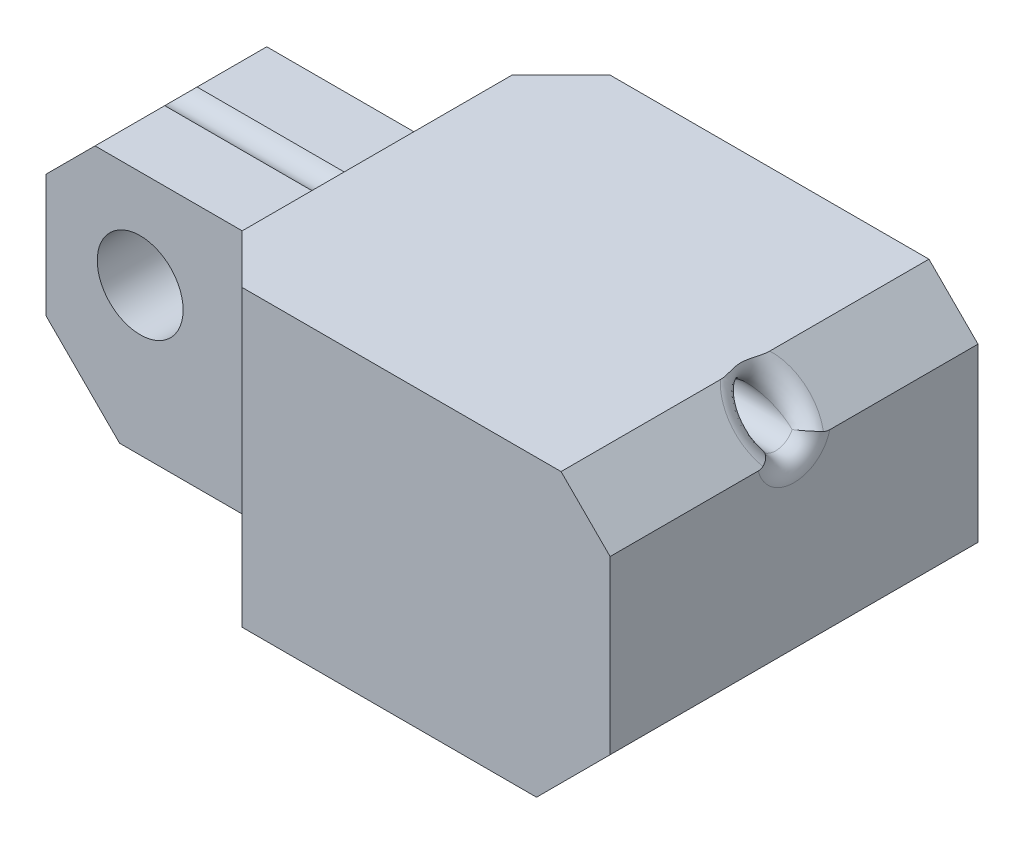
SolidWorks part; units mm, degrees
ref_plane "Спереди" through (0, 0, 0) normal (0, 0, 1) x (1, 0, 0)
ref_plane "Сверху" through (0, 0, 0) normal (0, 1, 0) x (1, 0, 0)
ref_plane "Справа" through (0, 0, 0) normal (1, 0, 0) x (0, 0, -1)
sketch "Эскиз2" plane through (0, 0, 0) normal (1, 0, 0) x (0, 0, -1)
  line L1 (-7.5, 6) -> (7.5, 6)
  line L2 (-7.5, 6) -> (-7.5, -6)
  line L3 (-7.5, -6) -> (7.5, -6)
  line L4 (7.5, 6) -> (7.5, -6)
  line L5 (-7.5, 6) -> (7.5, -6) construction
  line L6 (-7.5, -6) -> (7.5, 6) construction
  point P0 (0, 0)
extrude "Вытянуть1" add sketch "Эскиз2" along normal blind 27
sketch "Эскиз3" plane through (0, 6, 0) normal (0, 1, 0) x (1, 0, 0)
  line L0 (0, 0) -> (-9.2006, 0) construction
  line L1 (10, -9.9613) -> (10, -3.5)
  line L2 (-3.345, 9.9613) -> (10, 9.9613)
  line L3 (-3.345, 9.9613) -> (-3.345, 3.5)
  line L4 (-3.345, 3.5) -> (10, 3.5)
  line L5 (10, 9.9613) -> (10, 3.5)
  line L6 (-3.345, -9.9613) -> (10, -9.9613)
  line L7 (-3.345, -3.5) -> (10, -3.5)
  line L8 (-3.345, -9.9613) -> (-3.345, -3.5)
  line L9 (0, 7.5) -> (0, -7.5) construction
  dimension "D1" = 3.5
  dimension "D2" = 10
extrude "Вырез-Вытянуть1" cut sketch "Эскиз3" against normal through all
sketch "Эскиз4" plane through (0, 0, 3.5) normal (0, 0, 1) x (1, 0, 0)
  circle A0 centre (3.8399, 0) radius 1.75
extrude "Вытянуть2" cut sketch "Эскиз4" against normal through all
chamfer "Фаска4" distance 3 angle 45 1 edges at (27, -6, 0)
chamfer "Фаска5" distance 3 angle 45 1 edges at (0, -6, 0)
sketch "Эскиз8" plane through (0, 0, 0) normal (-1, 0, 0) x (0, 0, 1)
  line L0 (0, 6) -> (0, 2.0994) construction
  line L2 (-3.5, 6) -> (-7.5, 6) construction
  line L3 (-3.9395, 7.8642) -> (3.9729, 7.8642)
  line L4 (-3.9395, 7.8642) -> (-3.9395, 4)
  line L5 (-3.9395, 4) -> (3.9729, 4)
  line L6 (3.9729, 7.8642) -> (3.9729, 4)
  dimension "D1" = 2
extrude "Вытянуть4" cut sketch "Эскиз8" against normal blind 10
chamfer "Фаска6" distance 2 angle 45 1 edges at (0, 4, 0)
sketch "Эскиз10" plane through (27, 0, 0) normal (1, 0, 0) x (0, 0, -1)
  circle A0 centre (0, 4.3577) radius 0.75
extrude "Вырез-Вытянуть2" cut sketch "Эскиз10" against normal through all
fillet "Скругление1" radius 0.75 1 edges at (10, 5.1077, 0)
chamfer "Фаска7" distance 2 angle 45 1 edges at (27, 6, 0)
fillet "Скругление2" radius 0.75 2 edges at (27, 3.6077, 0) (25.8923, 5.1077, 0)
chamfer "Фаска8" distance 2 angle 45 2 edges at (10, 0, -7.5) (10, 0, 7.5)
